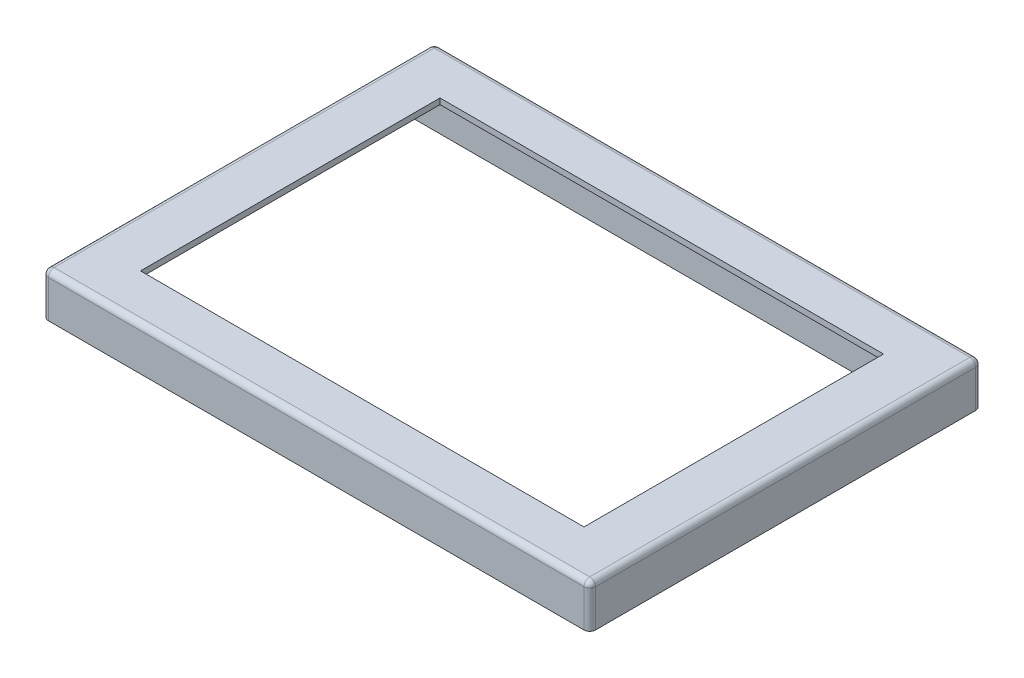
SolidWorks part; units mm, degrees
ref_plane "前视基准面" through (0, 0, 0) normal (0, 0, 1) x (1, 0, 0)
ref_plane "上视基准面" through (0, 0, 0) normal (0, 1, 0) x (1, 0, 0)
ref_plane "右视基准面" through (0, 0, 0) normal (1, 0, 0) x (0, 0, -1)
other "Configuration Table"
sketch "草图1" plane through (0, 0, 0) normal (0, 1, 0) x (1, 0, 0)
  line L29 (-47.5, -34) -> (47.5, -34)
  line L30 (-47.5, -34) -> (-47.5, 34)
  line L31 (-47.5, 34) -> (47.5, 34)
  line L32 (47.5, -34) -> (47.5, 34)
  line L33 (-47.5, -34) -> (47.5, 34) construction
  line L34 (-47.5, 34) -> (47.5, -34) construction
  point P0 (0, 0)
  dimension "D1" = 95
  dimension "D2" = 68
extrude "凸台-拉伸1" add sketch "草图1" along normal blind 7.5
sketch "草图2" plane through (0, 0, 0) normal (0, -1, 0) x (1, 0, 0)
  line L0 (-47.5, 34) -> (47.5, 34) construction
  line L5 (-45.5, 28.1) -> (40.5, 28.1)
  line L6 (-45.5, 28.1) -> (-45.5, 25)
  line L7 (-45.5, -28.1) -> (40.5, -28.1)
  line L8 (40.5, 28.1) -> (40.5, -28.1)
  line L9 (47.5, -34) -> (-47.5, -34) construction
  line L10 (-47.5, -34) -> (-47.5, 34) construction
  line L11 (47.5, 34) -> (47.5, -34) construction
  line L12 (-45.5, -18) -> (-45.5, -28.1)
  line L13 (-45.5, 25) -> (-46, 25)
  line L15 (-45.5, -18) -> (-46, -18)
  line L16 (-46, 25) -> (-46, -18)
  dimension "D1" = 5.9
  dimension "D2" = 5.9
  dimension "D3" = 2
  dimension "D4" = 7
  dimension "D5" = 3.1
  dimension "D6" = 10.1
  dimension "D7" = 0.5
extrude "切除-拉伸1" cut sketch "草图2" against normal blind 6.5
sketch "草图3" plane through (0, 7.5, 0) normal (0, 1, 0) x (1, 0, 0)
  line L0 (-47.5, 34) -> (-47.5, -34) construction
  line L1 (-38.5, 26) -> (38.5, 26)
  line L2 (-38.5, 26) -> (-38.5, -26)
  line L3 (-38.5, -26) -> (38.5, -26)
  line L4 (38.5, 26) -> (38.5, -26)
  line L5 (47.5, -34) -> (47.5, 34) construction
  line L6 (47.5, 34) -> (-47.5, 34) construction
  line L7 (-47.5, -34) -> (47.5, -34) construction
  dimension "D1" = 9
  dimension "D2" = 9
  dimension "D3" = 8
  dimension "D4" = 8
extrude "切除-拉伸2" cut sketch "草图3" against normal through all
sketch "草图4" plane through (0, 0, 0) normal (0, -1, 0) x (1, 0, 0)
  line L0 (-47.5, -34) -> (-47.5, 34) construction
  line L1 (-47.5, 34) -> (47.5, 34) construction
  line L2 (47.5, 34) -> (47.5, -34) construction
  line L3 (47.5, -34) -> (-47.5, -34) construction
  circle A0 centre (-44.5, 31) radius 2.1
  circle A1 centre (0, 31) radius 2.1
  circle A2 centre (44.5, 31) radius 2.1
  circle A3 centre (44.5, -31) radius 2.1
  circle A4 centre (0, -31) radius 2.1
  circle A5 centre (-44.5, -31) radius 2.1
  point P25 (0, 0)
  dimension "D1" = 2.1
  dimension "D2" = 2.1
  dimension "D3" = 2.1
  dimension "D4" = 2.1
  dimension "D5" = 2.1
  dimension "D6" = 2.1
  dimension "D7" = 3
  dimension "D8" = 3
  dimension "D9" = 3
  dimension "D10" = 3
extrude "切除-拉伸3" cut sketch "草图4" against normal blind 2.6
fillet "圆角1" radius 1 4 edges at (-47.5, 7.5, 0) (0, 7.5, -34) (47.5, 7.5, 0) (0, 7.5, 34)
fillet "圆角2" radius 1 8 edges at (47.2071, 7.2071, 33.7071) (47.2071, 7.2071, -33.7071) (-47.2071, 7.2071, -33.7071) (-47.2071, 7.2071, 33.7071) (47.5, 3.25, 34) (47.5, 3.25, -34) (-47.5, 3.25, -34) (-47.5, 3.25, 34)
